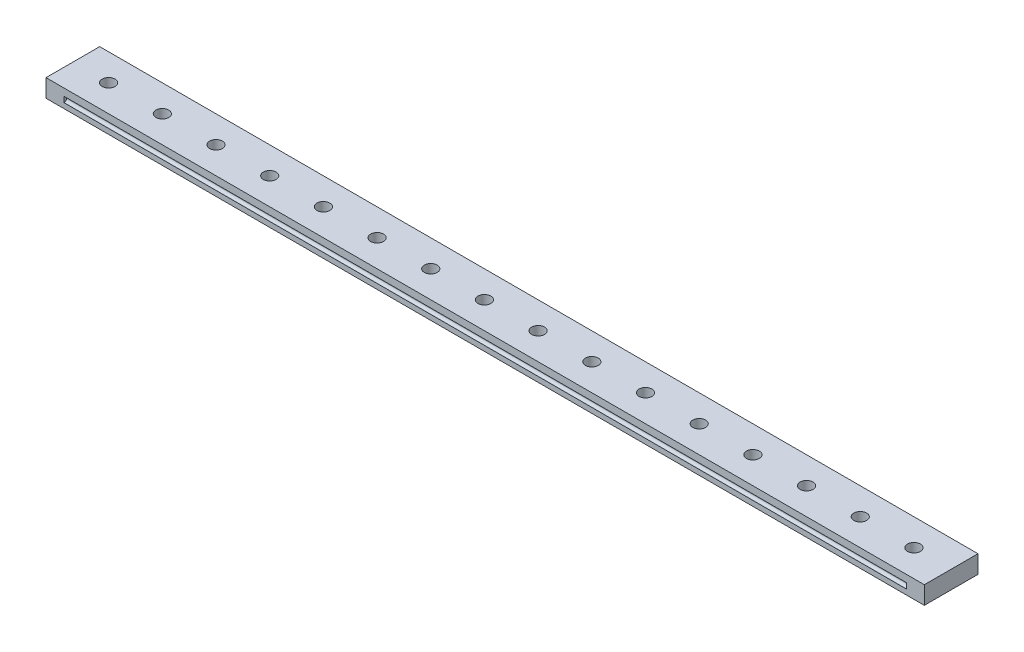
SolidWorks part; units mm, degrees
ref_plane "Front Plane" through (0, 0, 0) normal (0, 0, 1) x (1, 0, 0)
ref_plane "Top Plane" through (0, 0, 0) normal (0, 1, 0) x (1, 0, 0)
ref_plane "Right Plane" through (0, 0, 0) normal (1, 0, 0) x (0, 0, -1)
sketch "Sketch1" plane through (0, 0, 0) normal (0, 0, 1) x (1, 0, 0)
  line L1 (0, 0) -> (245.4, 0)
  line L2 (0, 0) -> (0, 5)
  line L3 (0, 5) -> (245.4, 5)
  line L4 (245.4, 0) -> (245.4, 5)
  dimension "D1" = 5
  dimension "D2" = 245.4
extrude "Main_Body" add sketch "Sketch1" along normal blind 15
sketch "Sketch3" plane through (0, 0, 0) normal (0, -1, 0) x (1, 0, 0)
  line L0 (0, 7.5) -> (10, 7.5) construction
  line L1 (0, 15) -> (0, 0) construction
  circle A0 centre (10, 7.5) radius 1.8
  circle A1 centre (25, 7.5) radius 1.8
  circle A2 centre (40, 7.5) radius 1.8
  circle A3 centre (55, 7.5) radius 1.8
  circle A4 centre (70, 7.5) radius 1.8
  circle A5 centre (85, 7.5) radius 1.8
  circle A6 centre (100, 7.5) radius 1.8
  circle A7 centre (115, 7.5) radius 1.8
  circle A8 centre (130, 7.5) radius 1.8
  circle A9 centre (145, 7.5) radius 1.8
  circle A10 centre (160, 7.5) radius 1.8
  circle A11 centre (175, 7.5) radius 1.8
  circle A12 centre (190, 7.5) radius 1.8
  circle A13 centre (205, 7.5) radius 1.8
  circle A14 centre (220, 7.5) radius 1.8
  circle A15 centre (235, 7.5) radius 1.8
  dimension "D1" = 3.6
  dimension "D2" = 10
  dimension "D3" = 16
extrude "Cut-Extrude2" cut sketch "Sketch3" against normal blind 5
sketch "Sketch4" plane through (0, 0, 0) normal (0, -1, 0) x (1, 0, 0)
  circle A0 centre (10, 7.5) radius 3
  circle A1 centre (25, 7.5) radius 3
  circle A2 centre (40, 7.5) radius 3
  circle A3 centre (55, 7.5) radius 3
  circle A4 centre (70, 7.5) radius 3
  circle A5 centre (85, 7.5) radius 3
  circle A6 centre (100, 7.5) radius 3
  circle A7 centre (115, 7.5) radius 3
  circle A8 centre (130, 7.5) radius 3
  circle A9 centre (145, 7.5) radius 3
  circle A10 centre (160, 7.5) radius 3
  circle A11 centre (175, 7.5) radius 3
  circle A12 centre (190, 7.5) radius 3
  circle A13 centre (205, 7.5) radius 3
  circle A14 centre (220, 7.5) radius 3
  circle A15 centre (235, 7.5) radius 3
  dimension "D1" = 6
  dimension "D2" = 16
extrude "Cut-Extrude3" cut sketch "Sketch4" against normal blind 2
sketch "Sketch2" plane through (0, 0, 15) normal (0, 0, 1) x (1, 0, 0)
  line L0 (0, 5) -> (0, 0) construction
  line L1 (5, 3) -> (240.4, 3)
  line L2 (5, 3) -> (5, 1.45)
  line L3 (5, 1.45) -> (240.4, 1.45)
  line L4 (240.4, 3) -> (240.4, 1.45)
  line L5 (245.4, 0) -> (245.4, 5) construction
  line L6 (245.4, 5) -> (0, 5) construction
  dimension "D1" = 5
  dimension "D2" = 1.55
  dimension "D3" = 5
  dimension "D4" = 2
extrude "Channel_A" cut sketch "Sketch2" against normal blind 0.75
fillet "Channel_A_Round" radius 0.7 2 edges at (122.7, 1.45, 14.25) (122.7, 3, 14.25)
